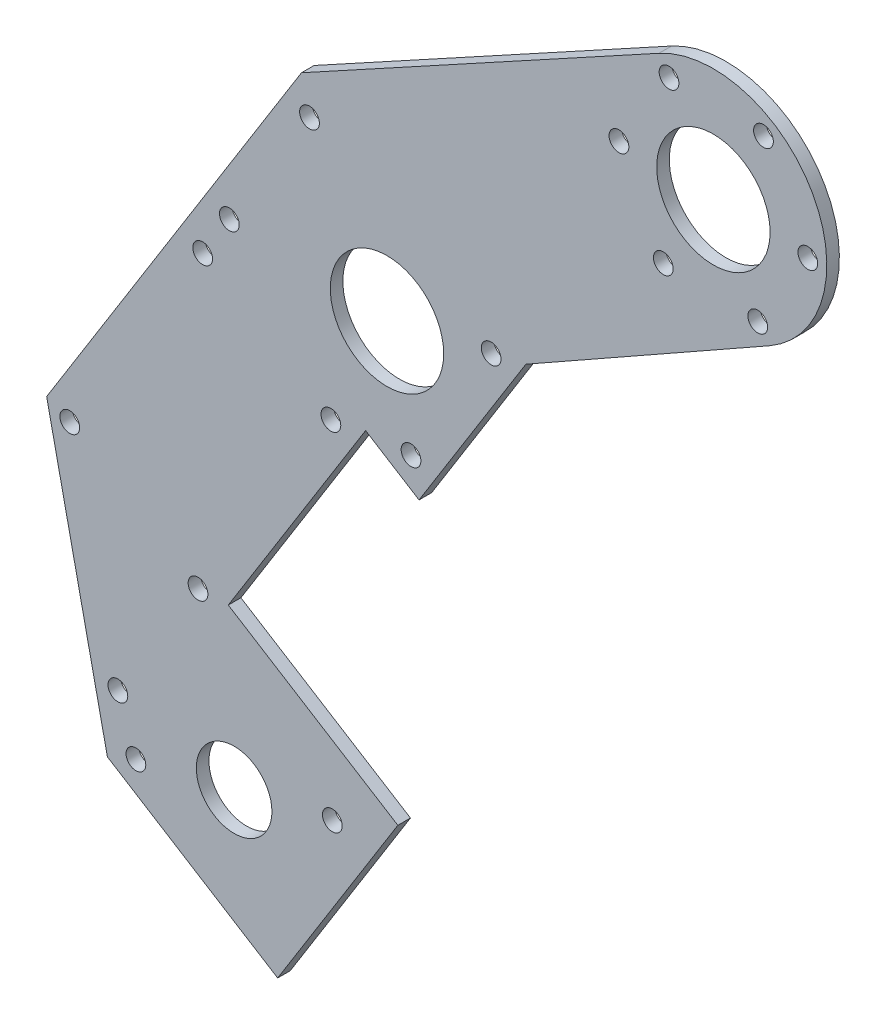
SolidWorks part; units mm, degrees
ref_plane "Front Plane" through (0, 0, 0) normal (0, 0, 1) x (1, 0, 0)
ref_plane "Top Plane" through (0, 0, 0) normal (0, 1, 0) x (1, 0, 0)
ref_plane "Right Plane" through (0, 0, 0) normal (1, 0, 0) x (0, 0, -1)
sketch "Sketch1" plane through (0, 0, -14.1946) normal (0, 0, 1) x (1, 0, 0)
  line L0 (-11.4036, 461.0409) -> (18.8813, 509.5069)
  line L1 (-54.3079, 487.8505) -> (-69.6155, 558.824)
  line L2 (18.8813, 509.5069) -> (-23.8465, 536.2061)
  line L4 (-11.4036, 461.0409) -> (-54.3079, 487.8505)
  line L5 (-69.6155, 558.824) -> (-5.4017, 661.5875)
  line L6 (-23.8465, 536.2061) -> (10.7592, 591.5868)
  line L10 (51.1419, 626.2552) -> (112.462, 660.9373)
  line L11 (10.7592, 591.5868) -> (24.222, 583.1743)
  line L13 (24.222, 583.1743) -> (51.1419, 626.2552)
  line L16 (-5.4017, 661.5875) -> (84.678, 710.8773)
  circle A2 centre (16.1415, 618.1747) radius 14.2875
  circle A3 centre (-22.3737, 496.6228) radius 9.525
  circle A5 centre (98.3945, 685.8096) radius 14.2875
  arc A7 (112.462, 660.9373) -> (84.678, 710.8773) centre (98.3945, 685.8096) ccw
  circle A8 centre (16.1415, 618.1747) radius 127.508 construction
  point P12 (-22.3737, 496.6228)
  point P33 (98.3945, 685.8096)
extrude "Boss-Extrude1" add sketch "Sketch1" along normal blind 3.175
sketch "Sketch17" plane through (0, 0, -11.0196) normal (0, 0, 1) x (1, 0, 0)
  line L0 (-47.1227, 490.909) -> (-22.3737, 496.6228)
  line L1 (-22.3737, 496.6228) -> (2.3753, 502.3365)
  line L2 (16.1415, 618.1747) -> (37.6819, 604.7147) construction
  line L12 (24.222, 583.1743) -> (51.1419, 626.2552) construction
  line L13 (37.6819, 604.7147) -> (27.587, 588.5594) construction
  line L14 (27.587, 588.5594) -> (22.2019, 591.9244) construction
  line L15 (22.2019, 591.9244) -> (-28.9566, 623.8918) construction
  line L16 (-5.4017, 661.5875) -> (-69.6155, 558.824) construction
  line L17 (-28.9566, 623.8918) -> (-23.5715, 620.5268) construction
  line L18 (-23.5715, 620.5268) -> (-3.3816, 652.8374) construction
  line L19 (-3.3816, 652.8374) -> (42.3918, 624.2351) construction
  line L20 (10.7592, 591.5868) -> (5.3741, 594.9518) construction
  line L21 (5.3741, 594.9518) -> (-31.4748, 535.9811) construction
  line L22 (-31.4748, 535.9811) -> (-51.6648, 503.6705) construction
  line L23 (5.3741, 594.9518) -> (2.0091, 589.5667) construction
  line L24 (-31.4748, 535.9811) -> (-63.7855, 556.1711) construction
  line L25 (2.0091, 589.5667) -> (-30.3015, 609.7566) construction
  circle A0 centre (-22.3737, 496.6228) radius 25.4
  dimension "D1" = 50.8
hole_wizard "#10 Clearance Hole2" positions "Sketch20" profile "Sketch21" hole size "#10" standard "ANSI Inch" end condition through all
sketch "Sketch20" plane through (0, 0, -11.0196) normal (0, 0, 1) x (1, 0, 0)
  point P0 (2.3753, 502.3365)
  point P3 (-47.1227, 490.909)
  point P24 (-3.3816, 652.8374)
  point P27 (42.3918, 624.2351)
  point P30 (22.2019, 591.9244)
  point P33 (-23.5715, 620.5268)
  point P42 (-31.4748, 535.9811)
  point P45 (-63.7855, 556.1711)
  point P48 (-51.6648, 503.6705)
  point P54 (2.0091, 589.5667)
  point P57 (-30.3015, 609.7566)
sketch "Sketch21" plane through (2.3753, 502.3365, -11.0196) normal (1, 0, 0) x (0, -1, 0)
  line L0 (0, 0) -> (0, 3.175)
  line L1 (0, 3.175) -> (2.4892, 3.175)
  line L2 (2.4892, 3.175) -> (2.4892, 0)
  line L5 (2.4892, 0) -> (0, 0)
  line L11 (0, -6.35) -> (0, 107.95) construction
  dimension "Thru Hole Dia." = 4.9784
  dimension "Thru Hole Depth" = 3.175
sketch "Sketch22" plane through (0, 0, -11.0196) normal (0, 0, 1) x (1, 0, 0)
  line L0 (98.3945, 685.8096) -> (111.0132, 706.0038) construction
  line L2 (111.0132, 706.0038) -> (87.2152, 706.8348) construction
  line L3 (87.2152, 706.8348) -> (74.5965, 686.6407) construction
  line L4 (74.5965, 686.6407) -> (85.7758, 665.6155) construction
  line L5 (85.7758, 665.6155) -> (109.5738, 664.7845) construction
  line L6 (109.5738, 664.7845) -> (122.1925, 684.9786) construction
  line L7 (122.1925, 684.9786) -> (111.0132, 706.0038) construction
  circle A0 centre (98.3945, 685.8096) radius 23.8125 construction
hole_wizard "#10 Clearance Hole3" positions "Sketch23" profile "Sketch24" hole size "#10" standard "ANSI Inch" end condition through all
sketch "Sketch23" plane through (0, 0, -11.0196) normal (0, 0, 1) x (1, 0, 0)
  point P0 (111.0132, 706.0038)
  point P3 (122.1925, 684.9786)
  point P6 (109.5738, 664.7845)
  point P9 (85.7758, 665.6155)
  point P12 (74.5965, 686.6407)
  point P15 (87.2152, 706.8348)
sketch "Sketch24" plane through (111.0132, 706.0038, -11.0196) normal (1, 0, 0) x (0, -1, 0)
  line L0 (0, 0) -> (0, 3.175)
  line L1 (0, 3.175) -> (2.4892, 3.175)
  line L2 (2.4892, 3.175) -> (2.4892, 0)
  line L5 (2.4892, 0) -> (0, 0)
  line L11 (0, -6.35) -> (0, 107.95) construction
  dimension "Thru Hole Dia." = 4.9784
  dimension "Thru Hole Depth" = 3.175
